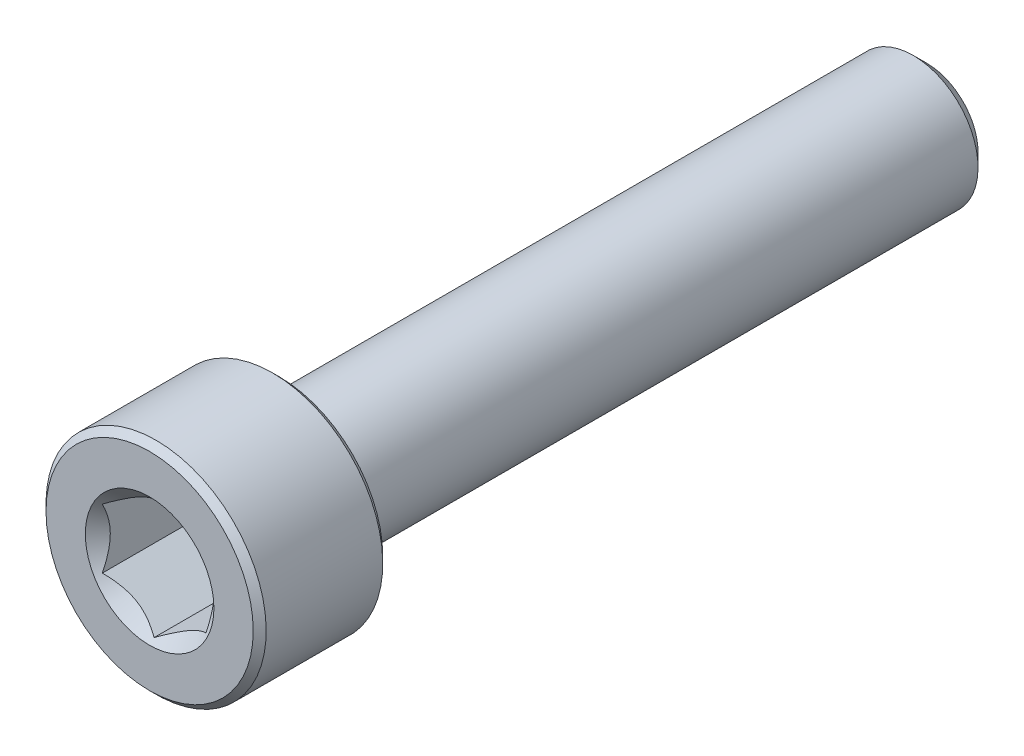
SolidWorks part; units mm, degrees
ref_plane "Front Plane" through (0, 0, 0) normal (0, 0, 1) x (1, 0, 0)
ref_plane "Top Plane" through (0, 0, 0) normal (0, 1, 0) x (1, 0, 0)
ref_plane "Right Plane" through (0, 0, 0) normal (1, 0, 0) x (0, 0, -1)
sketch "Sketch1" plane through (0, 0, 0) normal (1, 0, 0) x (0, 0, -1)
  line L0 (-15, 0) -> (15, 0) construction
  line L1 (15, 0) -> (15, 1.9804) construction
  line L2 (15, 1.9804) -> (14.4804, 2.5) construction
  line L3 (14.4804, 2.5) -> (14.4, 2.5) construction
  line L4 (14.4, 2.5) -> (-10, 2.5) construction
  line L5 (-10, 2.5) -> (-10, 4.25) construction
  line L6 (-10, 4.25) -> (-15, 4.25) construction
  line L7 (-15, 4.25) -> (-15, 0) construction
  line L8 (15, 1.9804) -> (15, 2.5) construction
  line L9 (14.95, 2.5866) -> (15.35, 1.8938) construction
  line L10 (15.35, 1.8938) -> (15.75, 2.5866) construction
  line L11 (15.75, 2.5866) -> (14.95, 2.5866) construction
  line L12 (15.35, 2.5866) -> (15.35, 2.5) construction
  line L13 (15.35, 1.8938) -> (15.35, 1.9804) construction
  line L14 (15.3, 1.9804) -> (15.4, 1.9804) construction
  line L15 (15, 2.5) -> (15.7, 2.5) construction
  line L16 (14.975, 2.5433) -> (15.725, 2.5433) construction
  line L17 (15, 0) -> (15, -2.5) construction
  line L18 (-10.25, 4.25) -> (-10, 4) construction
  line L19 (-14.75, 4.25) -> (-15, 4) construction
  line L20 (-10, 2.5) -> (-10, 0) construction
  line L21 (-10, 1.25) -> (-1.6667, 1.25) construction
  line L22 (-1.6667, 1.25) -> (6.6667, 1.25) construction
  line L23 (6.6667, 1.25) -> (15, 1.25) construction
  line L24 (-1.6667, 1.25) -> (-1.6667, 2.5) construction
  line L25 (-1.6667, 2.5) -> (-1.6667, 4.25) construction
  line L26 (6.6667, 1.25) -> (6.6667, 4.25) construction
  point P0 (-15, 2)
  point P3 (13, 2.5)
  point P4 (0, 0)
  point P18 (6.6667, 2.5)
  point P22 (15.35, 1.9804)
  point P24 (14.4, 2.5)
  point P25 (15.35, 2.5)
  point P28 (15.35, 2.5433)
  point P29 (13, -2.5)
  point P30 (-1.6667, 2.5)
  point P31 (-12.5, 4.25)
  point P37 (-10.875, 4.25)
  point P38 (-14.625, 4.25)
  point P45 (-1.6667, 1.25)
  point P46 (6.6667, 1.25)
  dimension "D2" = 0.1
  dimension "D7" = 0.25
  dimension "D8" = 0.25
  dimension "D9" = 0.25
  dimension "D10" = 0.125
  dimension "D11" = 0.625
  dimension "Drive Size" = 4
  dimension "Head Diameter" = 8.5
  dimension "Head Height" = 5
  dimension "Thread Pitch" = 0.8
  dimension "Thread Dia" = 5
  dimension "Length" = 25
  dimension "D12" = 0.6
  dimension "D4" = 2
  dimension "D3" = 45
sketch "Sketch2" plane through (0, 0, 0) normal (1, 0, 0) x (0, 0, -1)
  line L0 (-15, 0) -> (-15, 4)
  line L1 (-14.75, 4.25) -> (-10.25, 4.25)
  line L2 (-10, 4) -> (-10, 2.75)
  line L4 (14.4804, 2.5) -> (15, 1.9804)
  line L5 (15, 1.9804) -> (15, 0)
  line L6 (-10, 4.25) -> (-15, 4.25) construction
  line L7 (15, 0) -> (-15, 0)
  line L8 (-14.75, 4.25) -> (-15, 4) construction
  line L10 (-14.75, 4.25) -> (-15, 4)
  line L14 (-10.25, 4.25) -> (-10, 4) construction
  line L16 (-10.25, 4.25) -> (-10, 4)
  line L17 (-10, 2.5) -> (-10, 4.25) construction
  line L19 (-9.75, 2.5) -> (14.4804, 2.5)
  line L20 (14.4, 2.5) -> (-10, 2.5) construction
  arc A1 (-10, 2.75) -> (-9.75, 2.5) centre (-9.75, 2.75) ccw
  dimension "D3" = 0.25
revolve "Revolve1" add sketch "Sketch2" angle 360 about L7
sketch "Sketch3" plane through (0, 0, 15) normal (0, 0, 1) x (1, 0, 0)
  line L1 (2, -1.1547) -> (2, 1.1547)
  line L2 (2, 1.1547) -> (0, 2.3094)
  line L3 (0, 2.3094) -> (-2, 1.1547)
  line L4 (-2, 1.1547) -> (-2, -1.1547)
  line L5 (-2, -1.1547) -> (0, -2.3094)
  line L6 (0, -2.3094) -> (2, -1.1547)
  circle A0 centre (0, 0) radius 2 construction
  circle A1 centre (0, 0) radius 4.25 construction
  circle A2 centre (0, 0) radius 4.25 construction
  circle A3 centre (0, 0) radius 2.3094 construction
  point P13 (0, 0)
  dimension "D1" = 4.6188
extrude "Cut-Extrude1" cut sketch "Sketch3" against normal offset from surface (4 mm away) 1 up to face at (0, 4, 10)
sketch "Sketch4" plane through (0, 0, 15) normal (0, 0, 1) x (1, 0, 0)
  circle A0 centre (0, 0) radius 2.4826
  dimension "D1" = 4.9652
extrude "Cut-Extrude2" cut sketch "Sketch4" against normal up to vertex (2.5 mm away) draft 45 up to point (0, 4.25, 12.5)
sketch "Sketch11" plane through (0, 0, 0) normal (1, 0, 0) x (0, 0, -1)
  line L0 (-15, 0) -> (15, 0) construction
  line L1 (-15, 0) -> (15, 0) construction
  line L2 (-5.3125, 0) -> (-5.3125, 2.5) construction
  line L3 (14.4, 2.5) -> (-10, 2.5) construction
  line L4 (10.3125, 0) -> (10.3125, 2.5) construction
  line L6 (15, 1.9804) -> (15, 2.5) construction
  point P2 (-5.3125, 0)
  point P3 (10.3125, 0)
  dimension "D1" = 4.6875
  dimension "D2" = 4.6875
sketch "Sketch6" [suppressed] plane through (0, 0, -15) normal (0, 0, -1) x (-1, 0, 0)
  circle A0 centre (0, 0) radius 2.5
curve "Helix/Spiral1" [suppressed] pitch 0.8 height 25.8 turns 32.25
sketch "Sketch10" [suppressed] plane through (0, 0, 0) normal (1, 0, 0) x (0, 0, -1)
  line L0 (-9.75, -4.25) -> (-9.75, 4.25)
  line L5 (-15, 0) -> (15, 0) construction
  line L6 (-9.75, 2.5) -> (-9.75, -2.5) construction
  point P3 (-9.75, 0)
split "Split1" [suppressed] bodies to split 106
sketch "Sketch7" [suppressed] plane through (0, 0, 0) normal (1, 0, 0) x (0, 0, -1)
  line L0 (14.975, 2.5433) -> (15.725, 2.5433)
  line L1 (15.725, 2.5433) -> (15.4, 1.9804)
  line L2 (15.4, 1.9804) -> (15.3, 1.9804)
  line L3 (15.3, 1.9804) -> (14.975, 2.5433)
sweep "Cut-Sweep1" [suppressed] cut profiles "Sketch7" path "Helix/Spiral1"
sketch "Sketch8" [suppressed] plane through (0, 0, 0) normal (1, 0, 0) x (0, 0, -1)
  line L0 (-10, 0) -> (-10, 2.5)
  line L1 (-9.75, -2.5) -> (-9.75, 2.5) construction
  line L2 (-10, 2.5) -> (-9.75, 2.5)
  line L4 (-9.75, 2.5) -> (-8.3066, 0)
  line L5 (-8.3066, 0) -> (-10, 0)
  line L6 (14.4, 2.5) -> (-10, 2.5) construction
  line L7 (-15, 0) -> (15, 0) construction
  dimension "D1" = 60
revolve "Revolve2" [suppressed] add sketch "Sketch8" angle 360 about L5
equation "\"D2@Sketch1\" = \"Thread Pitch@Sketch1\" / 8"
equation "\"D4@Helix/Spiral1\" = \"Thread Pitch@Sketch1\""
equation "\"D7@Sketch1\" = \"Head Height@Sketch1\" * .05"
equation "\"D8@Sketch1\"=\"D7@Sketch1\""
equation "\"D9@Sketch1\"=\"D7@Sketch1\""
equation "\"D10@Sketch1\"=\"D7@Sketch1\"/2"
equation "\"D11@Sketch1\"=\"D10@Sketch1\"*5"
equation "\"D4@Sketch1\"=\"Thread Pitch@Sketch1\"*2.5"
equation "\"D12@Sketch1\"=\"Thread Pitch@Sketch1\"*.75"
equation "\"D3@Helix/Spiral1\"=\"Length@Sketch1\"+\"Thread Pitch@Sketch1\""
equation "\"D3@Sketch2\"=\"Thread Dia@Sketch1\"*0.05"
equation "\"D1@Sketch11\"=\"Length@Sketch1\"*0.1875"
equation "\"D2@Sketch11\"=\"D1@Sketch11\""
equation "\"D1@Sketch4\"=\"D1@Sketch3\"*1.075"
